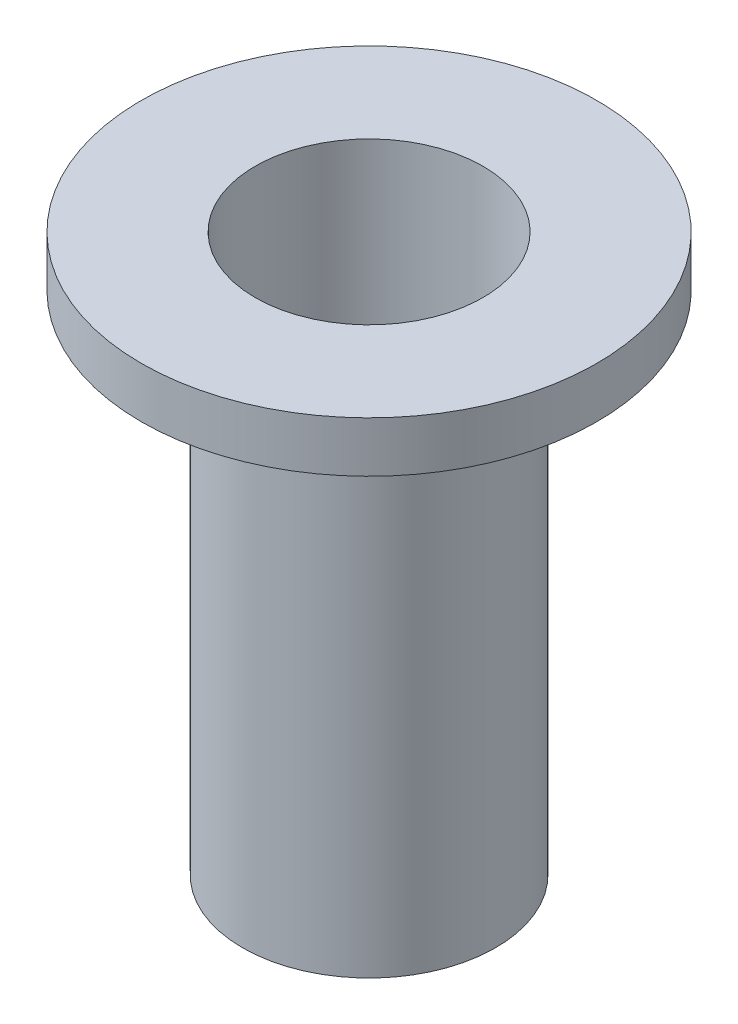
SolidWorks part; units mm, degrees
ref_plane "Front" through (0, 0, 0) normal (0, 0, 1) x (1, 0, 0)
ref_plane "Top" through (0, 0, 0) normal (0, 1, 0) x (1, 0, 0)
ref_plane "Right" through (0, 0, 0) normal (1, 0, 0) x (0, 0, -1)
sketch "Sketch1" plane through (0, 0, 0) normal (0, 1, 0) x (1, 0, 0)
  circle A0 centre (0, 0) radius 2.5
  circle A1 centre (0, 0) radius 2.25
  dimension "D1" = 5
  dimension "D2" = 4.5
extrude "Boss-Extrude1" add sketch "Sketch1" along normal blind 10
sketch "Sketch2" plane through (0, 10, 0) normal (0, 1, 0) x (1, 0, 0)
  circle A0 centre (0, 0) radius 2.25
  circle A1 centre (0, 0) radius 4.5
  circle A2 centre (0, 0) radius 2.25 construction
  dimension "D1" = 9
extrude "Boss-Extrude2" add sketch "Sketch2" along normal blind 1
sketch "Sketch7" plane through (0, 0, 0) normal (0, -1, 0) x (1, 0, 0)
  circle A0 centre (0, 0) radius 2.25
extrude "Boss-Extrude3" add sketch "Sketch7" against normal offset from surface (5.5 mm away) 5.5 up to face at (0, 11, 4.5)
sketch "Sketch8" plane through (0, 0, 0) normal (0, -1, 0) x (1, 0, 0)
  circle A0 centre (0, 0) radius 1.65
  point P0 (0, 0)
  dimension "D1" = 3.3
extrude "Cut-Extrude1" cut sketch "Sketch8" against normal through all
thread "Thread2" pitch 0.7 method cut profile "Thread Profile2" start angle 0, offset 1, length 10, pitch 0.7, diameter 3.3
ref_plane "Plane2" through (1.65, -1, 0) normal (0, 0, 1) x (1, 0, 0)
sketch "Thread Profile2" plane through (1.65, -1, 0) normal (0, 0, 1) x (1, 0, 0)
  line L0 (0, 0) -> (0, 0.7) construction
  line L1 (0, 0) -> (0.3789, 0.2187)
  line L2 (0.3789, 0.2187) -> (0.3789, 0.3062)
  line L3 (0.3789, 0.3062) -> (0, 0.525)
  line L4 (0.3789, 0.2625) -> (0, 0.2625) construction
  line L11 (0, 0) -> (0, 0.525)
  point P2 (0, 0)
  dimension "Pitch" = 0.7
  dimension "Profile_Angle" = 60
  dimension "Profile_Land" = 0.0875
  dimension "Profile_Height" = 0.3789
